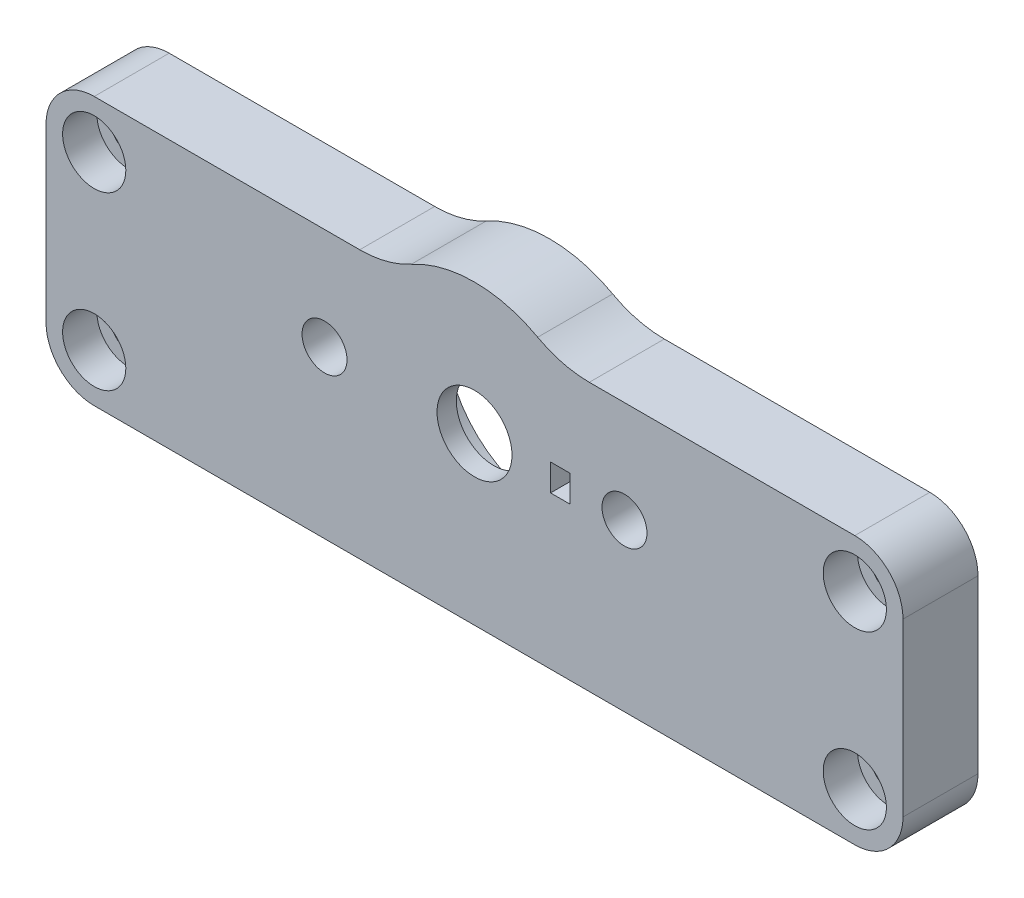
SolidWorks part; units mm, degrees
ref_plane "Front Plane" through (0, 0, 0) normal (0, 0, 1) x (1, 0, 0)
ref_plane "Top Plane" through (0, 0, 0) normal (0, 1, 0) x (1, 0, 0)
ref_plane "Right Plane" through (0, 0, 0) normal (1, 0, 0) x (0, 0, -1)
sketch "Sketch1" plane through (0, 0, 0) normal (0, 0, 1) x (1, 0, 0)
  line L0 (0, 0) -> (-40, 0) construction
  line L2 (-35.5, 9.5) -> (-7.7339, 9.5)
  line L3 (0, 0) -> (0, 12.25) construction
  line L6 (35.5, -15.5) -> (-35.5, -15.5)
  line L7 (-40, -11) -> (-40, 5)
  line L8 (35.5, 9.5) -> (7.7339, 9.5)
  line L10 (40, -11) -> (40, 5)
  circle A0 centre (0, 0) radius 9.75
  arc A1 (-7.7339, 9.5) -> (7.7339, 9.5) centre (0, 0) cw
  arc A16 (-35.5, -15.5) -> (-40, -11) centre (-35.5, -11) cw
  arc A17 (-40, 5) -> (-35.5, 9.5) centre (-35.5, 5) cw
  circle A18 centre (-35.5, 5) radius 1.65
  circle A25 centre (35.5, 5) radius 1.65
  arc A26 (40, 5) -> (35.5, 9.5) centre (35.5, 5) ccw
  arc A27 (35.5, -15.5) -> (40, -11) centre (35.5, -11) ccw
  circle A29 centre (-35.5, -11) radius 1.65
  circle A31 centre (35.5, -11) radius 1.65
  point P3 (36.0158, -15.1566)
  point P7 (40, 5)
  point P10 (35.5, 5)
  point P12 (35.554, -11)
  dimension "D1" = 19.5
  dimension "D2" = 2.5
  dimension "D4" = 4.5
  dimension "D5" = 40
  dimension "D3" = 16
  dimension "D7" = 3.3
  dimension "D6" = 5
extrude "Boss-Extrude1" add sketch "Sketch1" along normal blind 7
fillet "Fillet1" radius 10 2 edges at (7.7339, 9.5, 3.5) (-7.7339, 9.5, 3.5)
sketch "Sketch2" plane through (0, 0, 7) normal (0, 0, 1) x (1, 0, 0)
  circle A0 centre (0, 0) radius 7.5
  circle A1 centre (0, 0) radius 9.75 construction
  circle A2 centre (0, 0) radius 9.75
  dimension "D1" = 15
extrude "Boss-Extrude2" add sketch "Sketch2" against normal blind 2
sketch "Sketch3" plane through (0, 0, 7) normal (0, 0, 1) x (1, 0, 0)
  circle A0 centre (0, 0) radius 3.5
  circle A1 centre (0, 0) radius 7.5
  circle A2 centre (0, 0) radius 7.5 construction
  dimension "D1" = 7
extrude "Boss-Extrude3" add sketch "Sketch3" against normal blind 1.8
sketch "Sketch4" plane through (0, 0, 7) normal (0, 0, 1) x (1, 0, 0)
  line L0 (0, 0) -> (8, 0) construction
  line L2 (7.1, -1.25) -> (8.9, -1.25)
  line L3 (7.1, -1.25) -> (7.1, 1.25)
  line L4 (7.1, 1.25) -> (8.9, 1.25)
  line L5 (8.9, -1.25) -> (8.9, 1.25)
  line L6 (7.1, -1.25) -> (8.9, 1.25) construction
  line L7 (7.1, 1.25) -> (8.9, -1.25) construction
  dimension "D1" = 1.8
  dimension "D2" = 2.5
  dimension "D3" = 8
extrude "Cut-Extrude1" cut sketch "Sketch4" against normal blind 2.5
sketch "Sketch5" plane through (0, 0, 7) normal (0, 0, 1) x (1, 0, 0)
  line L0 (0, 0) -> (0, 12.25) construction
  arc A0 (5.8993, 10.736) -> (-5.8993, 10.736) centre (0, 0) ccw construction
  circle A1 centre (-14, 0) radius 2.1
  circle A2 centre (14, 0) radius 2.1
  dimension "D1" = 4.2
  dimension "D2" = 14
extrude "Cut-Extrude2" cut sketch "Sketch5" against normal blind 3
sketch "Sketch6" plane through (0, 0, 7) normal (0, 0, 1) x (1, 0, 0)
  circle A0 centre (-35.5, 5) radius 2.95
  circle A1 centre (-35.5, -11) radius 2.95
  circle A2 centre (35.5, -11) radius 2.95
  circle A3 centre (35.5, 5) radius 2.95
  dimension "D1" = 5.9
extrude "Cut-Extrude3" cut sketch "Sketch6" against normal blind 3.2
